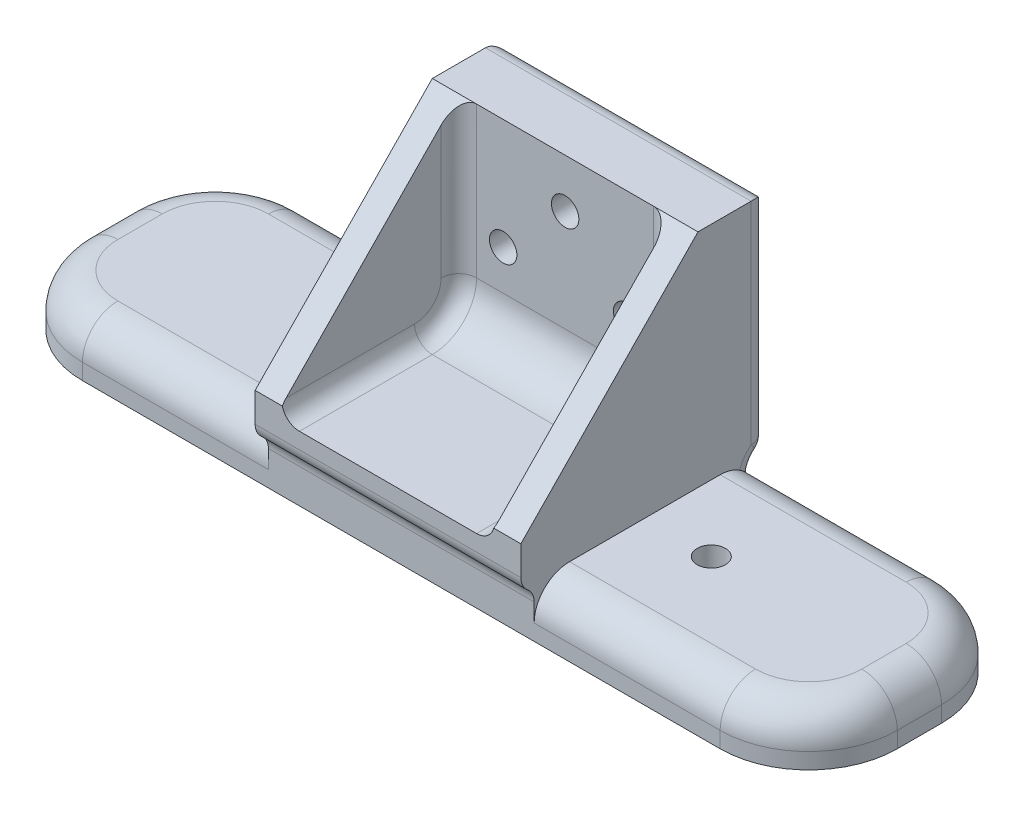
SolidWorks part; units mm, degrees
ref_plane "前视基准面" through (0, 0, 0) normal (0, 0, 1) x (1, 0, 0)
ref_plane "上视基准面" through (0, 0, 0) normal (0, 1, 0) x (1, 0, 0)
ref_plane "右视基准面" through (0, 0, 0) normal (1, 0, 0) x (0, 0, -1)
other "Configuration Table"
sketch "草图1" plane through (0, 0, 0) normal (0, 0, 1) x (1, 0, 0)
  line L0 (0, 0) -> (40891.4773, 0) construction
  line L1 (0, 0) -> (0, 40891.4773) construction
  line L3 (-15, 12.5) -> (15, 12.5)
  line L4 (-15, 12.5) -> (-15, -12.5)
  line L5 (-15, -12.5) -> (15, -12.5)
  line L6 (15, 12.5) -> (15, -12.5)
  line L7 (-15, 12.5) -> (15, -12.5) construction
  line L8 (-15, -12.5) -> (15, 12.5) construction
  point P5 (0, 0)
  dimension "D1" = 25
  dimension "D2" = 30
extrude "凸台-拉伸1" add sketch "草图1" along normal blind 28
sketch "草图2" plane through (0, 0, 0) normal (0, 0, -1) x (-1, 0, 0)
  line L0 (0, 0) -> (0, 50000) construction
  line L1 (0, 0) -> (50000, 0) construction
  circle A0 centre (0, 0) radius 7 construction
  circle A1 centre (0, 7) radius 1.55
  circle A3 centre (7, 0) radius 1.55
  circle A4 centre (-7, 0) radius 1.55
  dimension "D1" = 14
  dimension "D2" = 3.1
  dimension "D3" = 3.1
  dimension "D5" = 3.1
extrude "切除-拉伸1" cut sketch "草图2" against normal blind 8
sketch "草图4" plane through (0, -12.5, 0) normal (0, -1, 0) x (1, 0, 0)
  line L0 (-15, 14) -> (15, 14) construction
  line L1 (-15, 28) -> (-15, 0) construction
  line L2 (15, 28) -> (15, 0) construction
  line L3 (0, 0) -> (0, 28) construction
  line L4 (-15, 28) -> (15, 28) construction
  line L6 (-46, 26.5) -> (46, 26.5)
  line L7 (-46, 26.5) -> (-46, 1.5)
  line L8 (-46, 1.5) -> (46, 1.5)
  line L9 (46, 26.5) -> (46, 1.5)
  line L10 (-46, 26.5) -> (46, 1.5) construction
  line L11 (-46, 1.5) -> (46, 26.5) construction
  point P11 (0, 14)
  dimension "D1" = 92
  dimension "D2" = 25
extrude "凸台-拉伸2" add sketch "草图4" along normal blind 5.8
sketch "草图5" plane through (0, -18.3, 0) normal (0, -1, 0) x (1, 0, 0)
  line L0 (0, 1.5) -> (0, 26.5) construction
  line L1 (-15, 1.5) -> (15, 1.5) construction
  line L2 (15, 26.5) -> (-15, 26.5) construction
  line L3 (-46, 14) -> (46, 14) construction
  line L4 (-46, 26.5) -> (-46, 1.5) construction
  line L5 (46, 1.5) -> (46, 26.5) construction
  circle A0 centre (-22.5, 14) radius 1.6
  circle A1 centre (22.5, 14) radius 1.6
  dimension "D1" = 22.5
  dimension "D2" = 3.2
extrude "切除-拉伸2" cut sketch "草图5" against normal blind 35
sketch "草图6" plane through (0, 0, 28) normal (0, 0, 1) x (1, 0, 0)
  line L0 (15, 12.5) -> (-15, 12.5) construction
  line L1 (-12, 12.5) -> (12, 12.5)
  line L2 (-12, 12.5) -> (-12, -9.5)
  line L3 (-12, -9.5) -> (12, -9.5)
  line L4 (12, 12.5) -> (12, -9.5)
  line L5 (-15, 12.5) -> (-15, -12.5) construction
  line L6 (15, -12.5) -> (15, 12.5) construction
  line L7 (15, -12.5) -> (-15, -12.5) construction
  dimension "D1" = 3
  dimension "D2" = 3
  dimension "D3" = 3
extrude "切除-拉伸3" cut sketch "草图6" against normal blind 20
sketch "草图8" plane through (0, 12.5, 0) normal (0, 1, 0) x (1, 0, 0)
  line L0 (-12, -8) -> (-15, -8) construction
  line L1 (-15, -28) -> (-15, 0) construction
  line L2 (-15, -8) -> (15, -8) construction
  line L3 (15, -26.5) -> (15, -1.5) construction
sketch "草图9" plane through (15, 0, 0) normal (1, 0, 0) x (0, 0, -1)
  line L0 (-8, 12.5) -> (-28, -8)
  line L1 (-28, -12.5) -> (-28, 12.5) construction
  line L2 (-28, -12.5) -> (-26.5, -12.5) construction
  line L3 (-28, -8) -> (-28, 12.5)
  line L4 (-28, 12.5) -> (-8, 12.5)
  dimension "D1" = 4.5
extrude "切除-拉伸4" cut sketch "草图9" against normal blind 36
fillet "圆角1" radius 10 4 edges at (-46, -15.4, 1.5) (-46, -15.4, 26.5) (46, -15.4, 1.5) (46, -15.4, 26.5)
fillet "圆角2" radius 4 10 edges at (25.5, -12.5, 1.5) (43.0711, -12.5, 4.4289) (46, -12.5, 14) (43.0711, -12.5, 23.5711) (25.5, -12.5, 26.5) (-25.5, -12.5, 1.5) (-43.0711, -12.5, 4.4289) (-46, -12.5, 14) (-25.5, -12.5, 26.5) (-43.0711, -12.5, 23.5711)
fillet "圆角3" radius 2 1 edges at (0, -12.5, 1.5)
fillet "圆角4" radius 2 1 edges at (0, -12.5, 0)
fillet "圆角5" radius 2 9 edges at (15, -15.4682, 1.5) (15, -13.5705, 1.3028) (15, -12.18, 0.1972) (-15, -15.4682, 1.5) (-15, -13.5705, 1.3028) (-15, -12.18, 0.1972) (15, 0.593, 0) (0, 12.5, 0) (-15, 0.593, 0)
fillet "圆角6" radius 5 1 edges at (0, -9.5, 8)
fillet "圆角7" radius 2 6 edges at (-12, 4, 8) (-12, -8.0355, 9.4645) (12, 4, 8) (12, -8.0355, 9.4645) (-12, -9.5, 20.5) (12, -9.5, 20.5)
fillet "圆角8" radius 2 1 edges at (0, -12.5, 26.5)
fillet "圆角9" radius 2 1 edges at (0, -12.5, 28)
